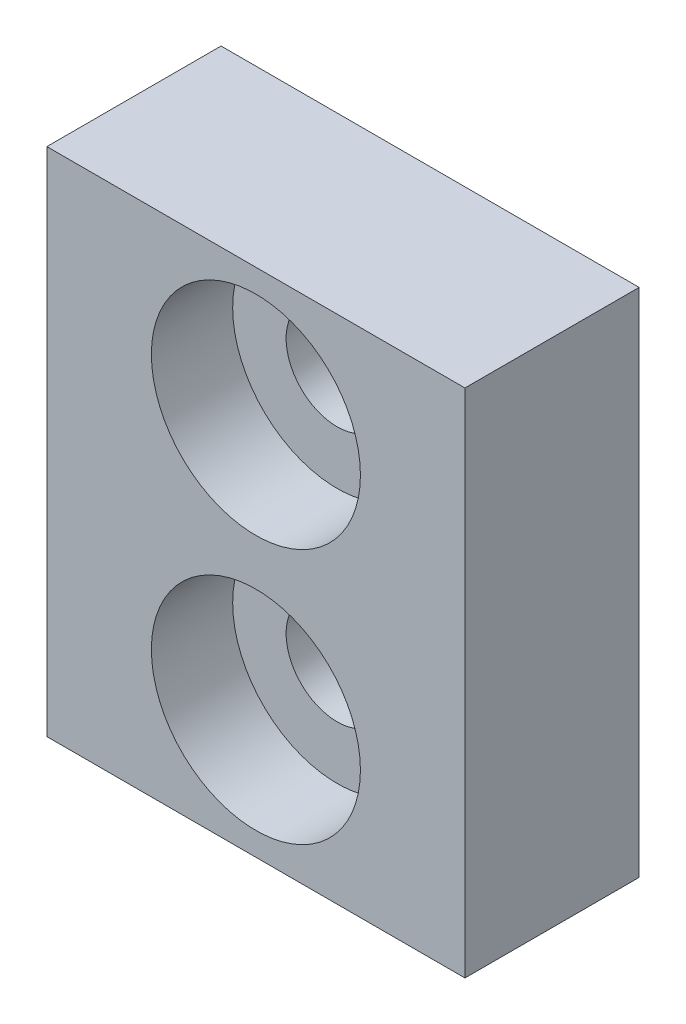
SolidWorks part; units mm, degrees
ref_plane "Ebene vorne" through (0, 0, 0) normal (0, 0, 1) x (1, 0, 0)
ref_plane "Ebene oben" through (0, 0, 0) normal (0, 1, 0) x (1, 0, 0)
ref_plane "Ebene rechts" through (0, 0, 0) normal (1, 0, 0) x (0, 0, -1)
sketch "Skizze1" plane through (0, 0, 0) normal (0, 0, 1) x (1, 0, 0)
  line L1 (-9, -5.5) -> (9, -5.5)
  line L2 (-9, -5.5) -> (-9, 5.5)
  line L3 (-9, 5.5) -> (9, 5.5)
  line L4 (9, -5.5) -> (9, 5.5)
  line L5 (-9, -5.5) -> (9, 5.5) construction
  line L6 (-9, 5.5) -> (9, -5.5) construction
  circle A0 centre (0, 0) radius 2.2
  point P0 (0, 0)
  dimension "D1" = 4.4
  dimension "D2" = 11
  dimension "D3" = 18
extrude "Aufsatz-Linear austragen1" add sketch "Skizze1" along normal blind 7.5
sketch "Skizze2" plane through (0, 0, 7.5) normal (0, 0, 1) x (1, 0, 0)
  circle A0 centre (0, 0) radius 4.5
  dimension "D1" = 9
extrude "Schnitt-Linear austragen1" cut sketch "Skizze2" against normal blind 3.5
mirror "Spiegeln1" about plane through (-9, -5.5, 7.5) normal (0, 1, 0) of bodies 102
